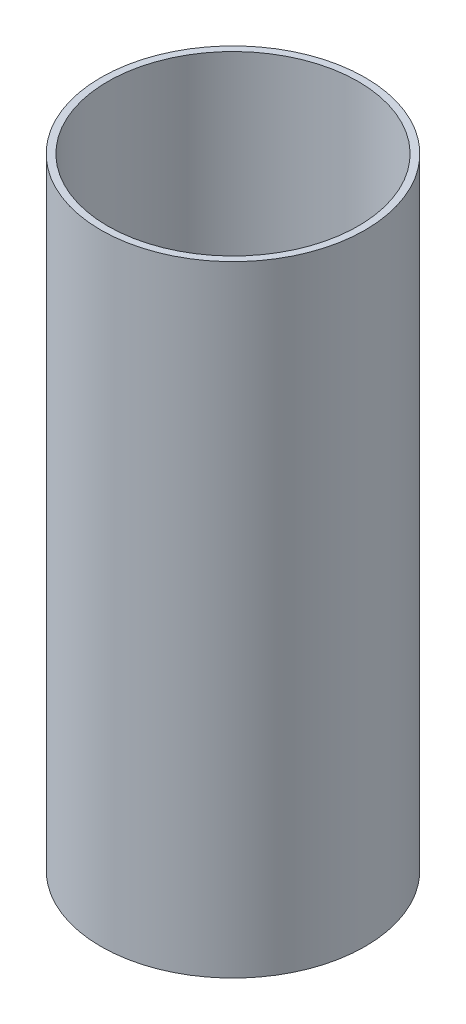
SolidWorks part; units mm, degrees
ref_plane "Front Plane" through (0, 0, 0) normal (0, 0, 1) x (1, 0, 0)
ref_plane "Top Plane" through (0, 0, 0) normal (0, 1, 0) x (1, 0, 0)
ref_plane "Right Plane" through (0, 0, 0) normal (1, 0, 0) x (0, 0, -1)
sketch "Sketch1" plane through (0, 0, 0) normal (0, 1, 0) x (1, 0, 0)
  circle A0 centre (0, 0) radius 54.5
  circle A1 centre (0, 0) radius 57.5
  dimension "D1" = 109
  dimension "D2" = 3
extrude "Boss-Extrude1" add sketch "Sketch1" along normal blind 270
sketch "Sketch2" plane through (-168.9329, 99.4365, -468.1144) normal (0, 0, 1) x (1, 0, 0)
  line L0 (111.4329, 170.5635) -> (111.4329, -99.4365) construction
  line L1 (111.4329, 150.5635) -> (226.4329, 150.5635) construction
  line L2 (111.4329, 150.5635) -> (111.4329, 50.5635) construction
  line L3 (111.4329, 50.5635) -> (226.4329, 50.5635) construction
  line L4 (226.4329, 150.5635) -> (226.4329, 50.5635) construction
  line L5 (226.4329, -99.4365) -> (226.4329, 170.5635) construction
  line L6 (118.4329, 143.5635) -> (118.4329, 57.5635)
  line L7 (118.4329, 57.5635) -> (219.4329, 57.5635)
  line L8 (219.4329, 143.5635) -> (219.4329, 57.5635)
  line L9 (118.4329, 143.5635) -> (219.4329, 143.5635)
  line L10 (111.4329, -99.4365) -> (226.4329, -99.4365) construction
  dimension "D2" = 250
  dimension "D3" = 100
  dimension "D1" = 7
